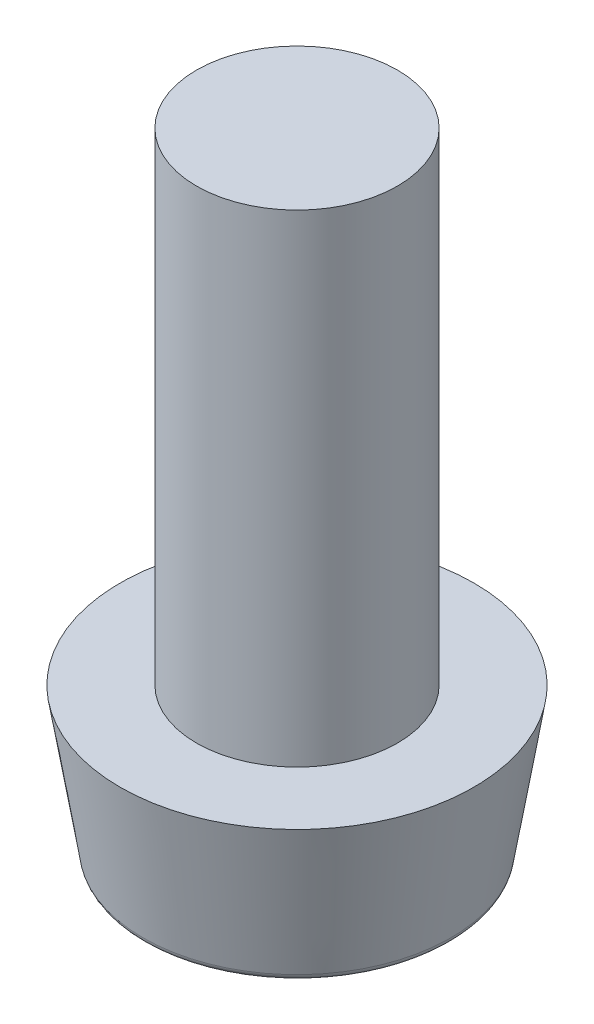
SolidWorks part; units mm, degrees
material "Nylon 101"
ref_plane "Plan de face" through (0, 0, 0) normal (0, 0, 1) x (1, 0, 0)
ref_plane "Plan de dessus" through (0, 0, 0) normal (0, 1, 0) x (1, 0, 0)
ref_plane "Plan de droite" through (0, 0, 0) normal (1, 0, 0) x (0, 0, -1)
sketch "Esquisse1" plane through (0, 0, 0) normal (0, 1, 0) x (1, 0, 0)
  circle A0 centre (0, 0) radius 2.2
  dimension "D1" = 4.4
extrude "Boss.-Extru.1" add sketch "Esquisse1" along normal blind 1.85
sketch "Esquisse2" plane through (0, 1.85, 0) normal (0, 1, 0) x (1, 0, 0)
  circle A0 centre (0, 0) radius 1.25
  dimension "D1" = 2.5
extrude "Boss.-Extru.2" add sketch "Esquisse2" along normal blind 6
chamfer "Chanfrein1" distance 0.3 distance2 1.85 1 edges at (0, 0, 2.2) first distance on face at (0, 0, 2.2)
fillet "Congé1" radius 0.1 1 edges at (0, 0, 1.9)
